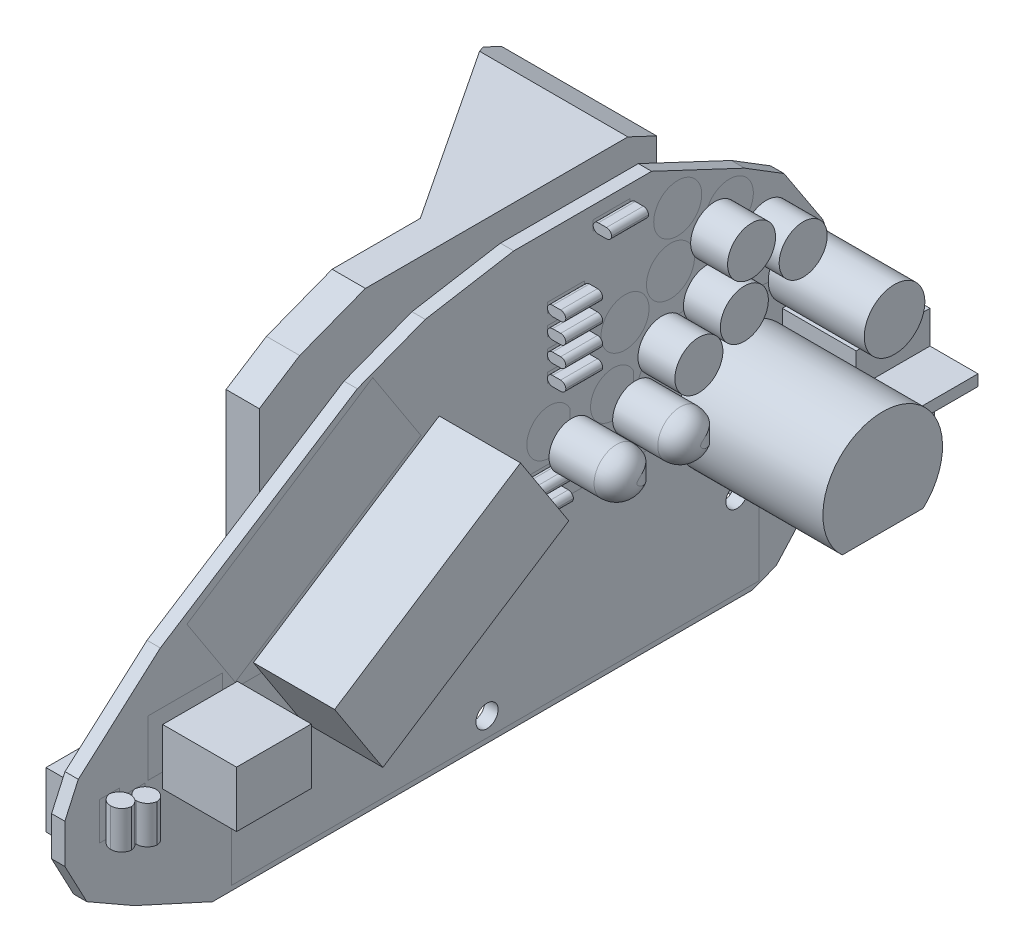
SolidWorks part; units mm, degrees
ref_plane "Alzado" through (0, 0, 0) normal (0, 0, 1) x (1, 0, 0)
ref_plane "Planta" through (0, 0, 0) normal (0, 1, 0) x (1, 0, 0)
ref_plane "Vista lateral" through (0, 0, 0) normal (1, 0, 0) x (0, 0, -1)
sketch "Croquis2" plane through (0, 0, 0) normal (1, 0, 0) x (0, 0, -1)
  line L0 (0.8299, 61.8219) -> (77.8633, 61.8219) construction
  line L1 (0, 0) -> (73, 0)
  line L2 (73, 0) -> (76.3008, 1.2365)
  line L3 (76.3008, 1.2365) -> (84.1489, 9.9615)
  line L4 (84.1489, 9.9615) -> (86.8383, 17.5094)
  line L5 (86.8383, 17.5094) -> (86.8383, 26.9193)
  line L6 (86.8383, 26.9193) -> (82.6155, 38.6955)
  line L7 (82.6155, 38.6955) -> (77.3688, 46.7034)
  line L9 (59.4482, 55.9264) -> (40.7811, 55.9264)
  line L10 (40.7811, 55.9264) -> (28.7946, 53.8855)
  line L11 (28.7946, 53.8855) -> (19.5987, 50.3479)
  line L12 (19.5987, 50.3479) -> (-7.0714, 33.2917)
  line L13 (-7.0714, 33.2917) -> (-18.1778, 23.4452)
  line L14 (-18.1778, 23.4452) -> (-19.9972, 19.4355)
  line L15 (-19.9972, 19.4355) -> (-19.9972, 14.1335)
  line L16 (-19.9972, 14.1335) -> (-17.0205, 8.5127)
  line L17 (-17.0205, 8.5127) -> (-10.6227, 4.8547)
  line L18 (-10.6227, 4.8547) -> (0, 0)
  line L19 (77.3688, 46.7034) -> (72.037, 49.9995)
  line L20 (72.037, 49.9995) -> (59.4482, 55.9264)
  dimension "D1" = 73
  dimension "D2" = 19.5987
  dimension "D3" = 28.7946
  dimension "D4" = 40.7811
  dimension "D5" = 59.4482
  dimension "D6" = 72.037
  dimension "D7" = 76.3008
  dimension "D8" = 77.3688
  dimension "D9" = 82.6155
  dimension "D10" = 84.1489
  dimension "D11" = 86.8383
  dimension "D12" = 7.0714
  dimension "D13" = 10.6227
  dimension "D14" = 17.0205
  dimension "D15" = 18.1778
  dimension "D16" = 19.9972
  dimension "D17" = 1.2365
  dimension "D18" = 4.8547
  dimension "D19" = 8.5127
  dimension "D20" = 9.9615
  dimension "D21" = 14.1335
  dimension "D22" = 17.5094
  dimension "D23" = 19.4355
  dimension "D24" = 23.4452
  dimension "D25" = 26.9193
  dimension "D26" = 33.2917
  dimension "D27" = 38.6955
  dimension "D28" = 46.7034
  dimension "D29" = 49.9995
  dimension "D30" = 50.3479
  dimension "D31" = 53.8855
  dimension "D32" = 55.9264
  dimension "D33" = 61.8219
sketch "Croquis4" plane through (0, 0, 0) normal (1, 0, 0) x (0, 0, -1)
  line L0 (-10.6227, 4.8547) -> (0, 0) construction
  line L1 (0, 0) -> (73, 0) construction
  line L2 (73, 0) -> (76.3008, 1.2365) construction
  line L3 (76.3008, 1.2365) -> (84.1489, 9.9615) construction
  line L4 (84.1489, 9.9615) -> (86.8383, 17.5094) construction
  line L5 (86.8383, 17.5094) -> (86.8383, 26.9193) construction
  line L6 (86.8383, 26.9193) -> (82.6155, 38.6955) construction
  line L7 (82.6155, 38.6955) -> (77.3688, 46.7034) construction
  line L8 (77.3688, 46.7034) -> (72.037, 49.9995) construction
  line L9 (72.037, 49.9995) -> (59.4482, 55.9264) construction
  line L10 (59.4482, 55.9264) -> (40.7811, 55.9264) construction
  line L11 (40.7811, 55.9264) -> (28.7946, 53.8855) construction
  line L12 (28.7946, 53.8855) -> (19.5987, 50.3479) construction
  line L13 (19.5987, 50.3479) -> (-7.0714, 33.2917) construction
  line L14 (-7.0714, 33.2917) -> (-18.1778, 23.4452) construction
  line L15 (-18.1778, 23.4452) -> (-19.9972, 19.4355) construction
  line L16 (-19.9972, 19.4355) -> (-19.9972, 14.1335) construction
  line L17 (-19.9972, 14.1335) -> (-17.0205, 8.5127) construction
  line L18 (-17.0205, 8.5127) -> (-10.6227, 4.8547) construction
  line L19 (-10.6227, 4.8547) -> (0, 0)
  line L20 (0, 0) -> (73, 0)
  line L21 (73, 0) -> (76.3008, 1.2365)
  line L22 (76.3008, 1.2365) -> (84.1489, 9.9615)
  line L23 (84.1489, 9.9615) -> (86.8383, 17.5094)
  line L24 (86.8383, 17.5094) -> (86.8383, 26.9193)
  line L25 (86.8383, 26.9193) -> (82.6155, 38.6955)
  line L26 (82.6155, 38.6955) -> (77.3688, 46.7034)
  line L27 (77.3688, 46.7034) -> (72.037, 49.9995)
  line L28 (72.037, 49.9995) -> (59.4482, 55.9264)
  line L29 (59.4482, 55.9264) -> (40.7811, 55.9264)
  line L30 (40.7811, 55.9264) -> (28.7946, 53.8855)
  line L31 (28.7946, 53.8855) -> (19.5987, 50.3479)
  line L32 (19.5987, 50.3479) -> (-7.0714, 33.2917)
  line L33 (-7.0714, 33.2917) -> (-18.1778, 23.4452)
  line L34 (-18.1778, 23.4452) -> (-19.9972, 19.4355)
  line L35 (-19.9972, 19.4355) -> (-19.9972, 14.1335)
  line L36 (-19.9972, 14.1335) -> (-17.0205, 8.5127)
  line L37 (-17.0205, 8.5127) -> (-10.6227, 4.8547)
extrude "Saliente-Extruir1" add sketch "Croquis4" along normal mid plane 1.8
sketch "Croquis5" plane through (0.9, 0, 0) normal (1, 0, 0) x (0, 0, -1)
  line L0 (-3.4698, 34.2759) -> (21.6903, 50.6151)
  line L1 (2.5913, 23.5294) -> (73.9913, 23.5294)
  line L2 (2.5913, 23.5294) -> (2.5913, 0.6294)
  line L3 (2.5913, 0.6294) -> (73.9913, 0.6294)
  line L4 (73.9913, 23.5294) -> (73.9913, 0.6294)
  line L5 (-8.7511, 26.1581) -> (1.3689, 26.1581)
  line L6 (-8.7511, 26.1581) -> (-8.7511, 18.5981)
  line L7 (-8.7511, 18.5981) -> (1.3689, 18.5981)
  line L8 (1.3689, 26.1581) -> (1.3689, 18.5981)
  line L9 (-15.2907, 19.6378) -> (-12.6307, 19.6378)
  line L10 (-15.2907, 19.6378) -> (-15.2907, 14.5278)
  line L11 (-15.2907, 14.5278) -> (-12.6307, 14.5278)
  line L12 (-12.6307, 19.6378) -> (-12.6307, 14.5278)
  line L13 (-11.8086, 18.4993) -> (-9.1486, 18.4993)
  line L14 (-11.8086, 18.4993) -> (-11.8086, 13.3893)
  line L15 (-11.8086, 13.3893) -> (-9.1486, 13.3893)
  line L16 (-9.1486, 18.4993) -> (-9.1486, 13.3893)
  line L17 (-3.4698, 34.2759) -> (3.0658, 24.2119)
  line L18 (21.6903, 50.6151) -> (28.226, 40.5511)
  line L19 (3.0658, 24.2119) -> (28.226, 40.5511)
  line L20 (0, 0) -> (73, 0) construction
  line L21 (75.6392, 27.0879) -> (85.7592, 27.0879)
  line L22 (75.6392, 27.0879) -> (75.6392, 19.5279)
  line L23 (75.6392, 19.5279) -> (85.7592, 19.5279)
  line L24 (85.7592, 27.0879) -> (85.7592, 19.5279)
  line L25 (74.1392, 28.0879) -> (84.1392, 28.0879)
  line L26 (74.1392, 28.0879) -> (74.1392, 34.0189)
  line L27 (74.1392, 34.0189) -> (84.1392, 34.0189)
  line L28 (84.1392, 28.0879) -> (84.1392, 34.0189)
  line L29 (48.3649, 30.915) -> (48.3649, 33.6844)
  line L30 (56.9859, 33.7818) -> (56.9859, 31.0124)
  line L32 (28.8788, 27.2935) -> (34.0788, 27.2935)
  line L33 (28.8788, 27.2935) -> (28.8788, 24.6435)
  line L34 (28.8788, 24.6435) -> (34.0788, 24.6435)
  line L35 (34.0788, 27.2935) -> (34.0788, 24.6435)
  line L36 (45.3296, 47.6238) -> (50.3296, 47.6238)
  line L37 (45.3296, 47.6238) -> (45.3296, 46.2938)
  line L38 (45.3296, 46.2938) -> (50.3296, 46.2938)
  line L39 (50.3296, 47.6238) -> (50.3296, 46.2938)
  line L40 (45.3296, 44.8838) -> (50.3296, 44.8838)
  line L41 (45.3296, 44.8838) -> (45.3296, 43.5538)
  line L42 (45.3296, 43.5538) -> (50.3296, 43.5538)
  line L43 (50.3296, 44.8838) -> (50.3296, 43.5538)
  line L44 (45.3296, 42.1438) -> (50.3296, 42.1438)
  line L45 (45.3296, 42.1438) -> (45.3296, 40.8138)
  line L46 (45.3296, 40.8138) -> (50.3296, 40.8138)
  line L47 (50.3296, 42.1438) -> (50.3296, 40.8138)
  line L48 (45.3296, 39.4038) -> (50.3296, 39.4038)
  line L49 (45.3296, 39.4038) -> (45.3296, 38.0738)
  line L50 (45.3296, 38.0738) -> (50.3296, 38.0738)
  line L51 (50.3296, 39.4038) -> (50.3296, 38.0738)
  line L52 (41.3607, 28.5694) -> (46.3607, 28.5694)
  line L53 (41.3607, 28.5694) -> (41.3607, 27.2394)
  line L54 (41.3607, 27.2394) -> (46.3607, 27.2394)
  line L55 (46.3607, 28.5694) -> (46.3607, 27.2394)
  line L56 (41.3607, 26.0194) -> (46.3607, 26.0194)
  line L57 (41.3607, 26.0194) -> (41.3607, 24.6894)
  line L58 (41.3607, 24.6894) -> (46.3607, 24.6894)
  line L59 (46.3607, 26.0194) -> (46.3607, 24.6894)
  line L60 (51.5296, 54.1938) -> (56.5296, 54.1938)
  line L61 (51.5296, 54.1938) -> (51.5296, 52.8638)
  line L62 (51.5296, 52.8638) -> (56.5296, 52.8638)
  line L63 (56.5296, 54.1938) -> (56.5296, 52.8638)
  circle A0 centre (65.2392, 29.5) radius 8.1
  circle A1 centre (75.3392, 39.1189) radius 4.1
  arc A2 (48.3649, 33.6844) -> (48.3649, 30.915) centre (45.6249, 32.2997) ccw
  arc A3 (56.9859, 33.7818) -> (56.9859, 31.0124) centre (54.2459, 32.3971) ccw
  circle A4 centre (69.9704, 46.5024) radius 3.25
  circle A5 centre (62.9828, 49.8363) radius 3.25
  circle A6 centre (62.0052, 42.9497) radius 3.25
  circle A7 centre (55.8488, 40.0099) radius 3.25
  point P37 (73.3392, 29.5)
  point P39 (75.3392, 35.0189)
  dimension "D25" = 16.2
  dimension "D28" = 8.2
  dimension "D31" = 6.14
  dimension "D53" = 6.5
  dimension "D1" = 71.4
  dimension "D2" = 22.9
  dimension "D3" = 2.5913
  dimension "D4" = 0.6294
  dimension "D5" = 10.12
  dimension "D6" = 7.56
  dimension "D7" = 18.5981
  dimension "D8" = 1.3689
  dimension "D9" = 2.66
  dimension "D10" = 5.11
  dimension "D11" = 14.5278
  dimension "D12" = 12.6307
  dimension "D13" = 13.3893
  dimension "D14" = 9.1486
  dimension "D15" = 12
  dimension "D16" = 30
  dimension "D17" = 33
  dimension "D18" = 24.2119
  dimension "D19" = 3.0658
  dimension "D20" = 19.5279
  dimension "D21" = 75.6392
  dimension "D22" = 1
  dimension "D23" = 5.931
  dimension "20" = 10
  dimension "D24" = 1.5
  dimension "D26" = 29.5
  dimension "D27" = 0.8
  dimension "D29" = 1
  dimension "D30" = 1.2
  dimension "D32" = 32.2997
  dimension "D33" = 44.256
  dimension "D34" = 8.621
  dimension "D35" = 0.0974
  dimension "D36" = 2.74
  dimension "D37" = 2.65
  dimension "D38" = 5.2
  dimension "D39" = 24.6435
  dimension "D40" = 28.8788
  dimension "D41" = 1.33
  dimension "D42" = 5
  dimension "D43" = 1.41
  dimension "D44" = 1.41
  dimension "D45" = 1.41
  dimension "D46" = 38.0738
  dimension "D47" = 25.3096
  dimension "D48" = 1.16
  dimension "D49" = 1.22
  dimension "D50" = 27.6307
  dimension "D51" = 1.2
  dimension "D52" = 5.24
  dimension "D54" = 55.8488
  dimension "D55" = 40.0099
  dimension "D56" = 6.1565
  dimension "D57" = 2.9399
  dimension "D58" = 6.8866
  dimension "D59" = 0.9775
  dimension "D60" = 6.9876
  dimension "D61" = 3.3339
split line "Línea de partición1"
sketch "Croquis6" plane through (-0.9, 0, 0) normal (-1, 0, 0) x (0, 0, 1)
  line L0 (-2.5913, 23.5294) -> (-2.5913, 0.6294) construction
  line L1 (-2.5913, 0.6294) -> (-73.9913, 0.6294) construction
  line L2 (-73.9913, 0.6294) -> (-73.9913, 23.5294) construction
  line L4 (-2.5913, 23.5294) -> (-2.5913, 0.6294)
  line L5 (-2.5913, 0.6294) -> (-73.9913, 0.6294)
  line L6 (-73.9913, 0.6294) -> (-73.9913, 23.5294)
  line L7 (-73.9913, 23.5294) -> (-2.5913, 23.5294)
  line L8 (8.7511, 18.5981) -> (-1.3689, 18.5981) construction
  line L9 (-81.9748, 18.5065) -> (-74.4148, 18.5065)
  line L10 (-81.9748, 18.5065) -> (-81.9748, 8.3865)
  line L11 (-81.9748, 8.3865) -> (-74.4148, 8.3865)
  line L12 (-74.4148, 18.5065) -> (-74.4148, 8.3865)
  line L13 (8.7511, 26.1581) -> (8.7511, 18.5981) construction
  line L14 (-85.7592, 27.0879) -> (-75.6392, 27.0879) construction
  line L15 (-75.6392, 27.0879) -> (-75.6392, 19.5279) construction
  line L17 (-1.3689, 13.2116) -> (8.7511, 13.2116)
  line L18 (-1.3689, 13.2116) -> (-1.3689, 5.6516)
  line L19 (-1.3689, 5.6516) -> (8.7511, 5.6516)
  line L20 (8.7511, 13.2116) -> (8.7511, 5.6516)
  line L21 (-67.93, 23.8894) -> (-14.13, 23.8894)
  line L22 (-67.93, 23.8894) -> (-67.93, 53.7694)
  line L23 (-67.93, 53.7694) -> (-14.13, 53.7694)
  line L24 (-14.13, 23.8894) -> (-14.13, 53.7694)
  dimension "D1" = 0.4234
  dimension "D2" = 5.0229
  dimension "D3" = 5.6516
  dimension "D4" = 29.88
  dimension "D5" = 53.8
  dimension "D6" = 0.36
  dimension "D7" = 14.13
split line "Línea de partición2"
sketch "Croquis7" plane through (0.9, 0, 0) normal (1, 0, 0) x (0, 0, -1)
  line L4 (1.3689, 26.1581) -> (-8.7511, 26.1581)
  line L5 (-8.7511, 26.1581) -> (-8.7511, 18.5981)
  line L6 (-8.7511, 18.5981) -> (1.3689, 18.5981)
  line L7 (1.3689, 18.5981) -> (1.3689, 26.1581)
  line L8 (1.3689, 26.1581) -> (-8.7511, 26.1581)
  line L9 (-8.7511, 26.1581) -> (-8.7511, 18.5981)
  line L10 (-8.7511, 18.5981) -> (1.3689, 18.5981)
  line L11 (1.3689, 18.5981) -> (1.3689, 26.1581)
  line L12 (85.7592, 27.0879) -> (75.6392, 27.0879)
  line L13 (75.6392, 27.0879) -> (75.6392, 19.5279)
  line L14 (75.6392, 19.5279) -> (85.7592, 19.5279)
  line L15 (85.7592, 19.5279) -> (85.7592, 27.0879)
  line L16 (85.7592, 27.0879) -> (75.6392, 27.0879)
  line L17 (75.6392, 27.0879) -> (75.6392, 19.5279)
  line L18 (75.6392, 19.5279) -> (85.7592, 19.5279)
  line L19 (85.7592, 19.5279) -> (85.7592, 27.0879)
  dimension "D1" = 0
  dimension "D2" = 0
extrude "Saliente-Extruir2" add sketch "Croquis7" along normal blind 10 from offset 2 separate body
sketch "Croquis8" plane through (0.9, 0, 0) normal (1, 0, 0) x (0, 0, -1)
  line L4 (21.6903, 50.6151) -> (-3.4698, 34.2759)
  line L5 (-3.4698, 34.2759) -> (3.0658, 24.2119)
  line L6 (3.0658, 24.2119) -> (28.226, 40.5511)
  line L7 (28.226, 40.5511) -> (21.6903, 50.6151)
  line L8 (21.6903, 50.6151) -> (-3.4698, 34.2759)
  line L9 (-3.4698, 34.2759) -> (3.0658, 24.2119)
  line L10 (3.0658, 24.2119) -> (28.226, 40.5511)
  line L11 (28.226, 40.5511) -> (21.6903, 50.6151)
  dimension "D1" = 0
extrude "Saliente-Extruir3" add sketch "Croquis8" along normal blind 11 from offset 9 separate body
sketch "Croquis9" plane through (0.9, 0, 0) normal (1, 0, 0) x (0, 0, -1)
  line L1 (59.7654, 23.5294) -> (70.7129, 23.5294)
  line L2 (59.7654, 23.5294) -> (70.7129, 23.5294)
  arc A1 (70.7129, 23.5294) -> (59.7654, 23.5294) centre (65.2392, 29.5) ccw
  arc A3 (70.7129, 23.5294) -> (59.7654, 23.5294) centre (65.2392, 29.5) ccw
  dimension "D1" = 0
extrude "Saliente-Extruir4" add sketch "Croquis9" along normal blind 20 from offset 5.5 separate body
sketch "Croquis10" plane through (0.9, 0, 0) normal (1, 0, 0) x (0, 0, -1)
  circle A0 centre (69.9704, 46.5024) radius 3.25 construction
  circle A1 centre (55.8488, 40.0099) radius 3.25
  circle A2 centre (55.8488, 40.0099) radius 3.25
  circle A3 centre (62.0052, 42.9497) radius 3.25
  circle A4 centre (62.0052, 42.9497) radius 3.25
  circle A5 centre (62.9828, 49.8363) radius 3.25 construction
  circle A6 centre (69.9704, 46.5024) radius 3.25
  circle A7 centre (62.9828, 49.8363) radius 3.25
  dimension "D1" = 0
  dimension "D2" = 0
extrude "Saliente-Extruir5" add sketch "Croquis10" along normal blind 5 from offset 5 separate body
sketch "Croquis11" plane through (0.9, 0, 0) normal (1, 0, 0) x (0, 0, -1)
  line L0 (34.0788, 27.2935) -> (28.8788, 27.2935) construction
  line L1 (28.8788, 27.2935) -> (28.8788, 24.6435) construction
  line L2 (28.8788, 24.6435) -> (34.0788, 24.6435) construction
  line L3 (34.0788, 24.6435) -> (34.0788, 27.2935) construction
  line L4 (-9.1486, 18.4993) -> (-11.8086, 18.4993) construction
  line L5 (-11.8086, 18.4993) -> (-11.8086, 13.3893) construction
  line L6 (-11.8086, 13.3893) -> (-9.1486, 13.3893) construction
  line L7 (-9.1486, 13.3893) -> (-9.1486, 18.4993) construction
  line L8 (-12.6307, 19.6378) -> (-15.2907, 19.6378) construction
  line L9 (-15.2907, 19.6378) -> (-15.2907, 14.5278) construction
  line L10 (-15.2907, 14.5278) -> (-12.6307, 14.5278) construction
  line L11 (-12.6307, 14.5278) -> (-12.6307, 19.6378) construction
  line L12 (34.0788, 27.2935) -> (28.8788, 27.2935)
  line L13 (28.8788, 27.2935) -> (28.8788, 24.6435)
  line L14 (28.8788, 24.6435) -> (34.0788, 24.6435)
  line L15 (34.0788, 24.6435) -> (34.0788, 27.2935)
  line L16 (-9.1486, 18.4993) -> (-11.8086, 18.4993)
  line L17 (-11.8086, 18.4993) -> (-11.8086, 13.3893)
  line L18 (-11.8086, 13.3893) -> (-9.1486, 13.3893)
  line L19 (-9.1486, 13.3893) -> (-9.1486, 18.4993)
  line L20 (-12.6307, 19.6378) -> (-15.2907, 19.6378)
  line L21 (-15.2907, 19.6378) -> (-15.2907, 14.5278)
  line L22 (-15.2907, 14.5278) -> (-12.6307, 14.5278)
  line L23 (-12.6307, 14.5278) -> (-12.6307, 19.6378)
extrude "Saliente-Extruir6" add sketch "Croquis11" along normal blind 3 separate body
fillet "Redondeo1" radius 1.5 4 edges at (3.9, 17.0828, 12.6307) (3.9, 17.0828, 15.2907) (0.9, 17.0828, 12.6307) (0.9, 17.0828, 15.2907)
fillet "Redondeo2" radius 1.5 4 edges at (0.9, 15.9443, 11.8086) (0.9, 15.9443, 9.1486) (3.9, 15.9443, 9.1486) (3.9, 15.9443, 11.8086)
fillet "Redondeo3" radius 1.5 4 edges at (0.9, 27.2935, -31.4788) (0.9, 24.6435, -31.4788) (3.9, 24.6435, -31.4788) (3.9, 27.2935, -31.4788)
sketch "Croquis12" plane through (0.9, 0, 0) normal (1, 0, 0) x (0, 0, -1)
  line L0 (46.3607, 26.0194) -> (41.3607, 26.0194) construction
  line L1 (41.3607, 26.0194) -> (41.3607, 24.6894) construction
  line L2 (41.3607, 24.6894) -> (46.3607, 24.6894) construction
  line L3 (46.3607, 24.6894) -> (46.3607, 26.0194) construction
  line L4 (46.3607, 28.5694) -> (41.3607, 28.5694) construction
  line L5 (41.3607, 28.5694) -> (41.3607, 27.2394) construction
  line L6 (41.3607, 27.2394) -> (46.3607, 27.2394) construction
  line L7 (46.3607, 27.2394) -> (46.3607, 28.5694) construction
  line L8 (50.3296, 39.4038) -> (45.3296, 39.4038) construction
  line L9 (45.3296, 39.4038) -> (45.3296, 38.0738) construction
  line L10 (45.3296, 38.0738) -> (50.3296, 38.0738) construction
  line L11 (50.3296, 38.0738) -> (50.3296, 39.4038) construction
  line L12 (50.3296, 42.1438) -> (45.3296, 42.1438) construction
  line L13 (45.3296, 42.1438) -> (45.3296, 40.8138) construction
  line L14 (45.3296, 40.8138) -> (50.3296, 40.8138) construction
  line L15 (50.3296, 40.8138) -> (50.3296, 42.1438) construction
  line L16 (50.3296, 44.8838) -> (45.3296, 44.8838) construction
  line L17 (45.3296, 44.8838) -> (45.3296, 43.5538) construction
  line L18 (45.3296, 43.5538) -> (50.3296, 43.5538) construction
  line L19 (50.3296, 43.5538) -> (50.3296, 44.8838) construction
  line L20 (50.3296, 47.6238) -> (45.3296, 47.6238) construction
  line L21 (45.3296, 47.6238) -> (45.3296, 46.2938) construction
  line L22 (45.3296, 46.2938) -> (50.3296, 46.2938) construction
  line L23 (50.3296, 46.2938) -> (50.3296, 47.6238) construction
  line L24 (56.5296, 54.1938) -> (51.5296, 54.1938) construction
  line L25 (51.5296, 54.1938) -> (51.5296, 52.8638) construction
  line L26 (51.5296, 52.8638) -> (56.5296, 52.8638) construction
  line L27 (56.5296, 52.8638) -> (56.5296, 54.1938) construction
  line L28 (46.3607, 26.0194) -> (41.3607, 26.0194)
  line L29 (41.3607, 26.0194) -> (41.3607, 24.6894)
  line L30 (41.3607, 24.6894) -> (46.3607, 24.6894)
  line L31 (46.3607, 24.6894) -> (46.3607, 26.0194)
  line L32 (46.3607, 28.5694) -> (41.3607, 28.5694)
  line L33 (41.3607, 28.5694) -> (41.3607, 27.2394)
  line L34 (41.3607, 27.2394) -> (46.3607, 27.2394)
  line L35 (46.3607, 27.2394) -> (46.3607, 28.5694)
  line L36 (50.3296, 39.4038) -> (45.3296, 39.4038)
  line L37 (45.3296, 39.4038) -> (45.3296, 38.0738)
  line L38 (45.3296, 38.0738) -> (50.3296, 38.0738)
  line L39 (50.3296, 38.0738) -> (50.3296, 39.4038)
  line L40 (50.3296, 42.1438) -> (45.3296, 42.1438)
  line L41 (45.3296, 42.1438) -> (45.3296, 40.8138)
  line L42 (45.3296, 40.8138) -> (50.3296, 40.8138)
  line L43 (50.3296, 40.8138) -> (50.3296, 42.1438)
  line L44 (50.3296, 44.8838) -> (45.3296, 44.8838)
  line L45 (45.3296, 44.8838) -> (45.3296, 43.5538)
  line L46 (45.3296, 43.5538) -> (50.3296, 43.5538)
  line L47 (50.3296, 43.5538) -> (50.3296, 44.8838)
  line L48 (50.3296, 47.6238) -> (45.3296, 47.6238)
  line L49 (45.3296, 47.6238) -> (45.3296, 46.2938)
  line L50 (45.3296, 46.2938) -> (50.3296, 46.2938)
  line L51 (50.3296, 46.2938) -> (50.3296, 47.6238)
  line L52 (56.5296, 54.1938) -> (51.5296, 54.1938)
  line L53 (51.5296, 54.1938) -> (51.5296, 52.8638)
  line L54 (51.5296, 52.8638) -> (56.5296, 52.8638)
  line L55 (56.5296, 52.8638) -> (56.5296, 54.1938)
extrude "Saliente-Extruir7" add sketch "Croquis12" along normal blind 2.5 separate body
fillet "Redondeo4" radius 0.7 4 edges at (0.9, 28.5694, -43.8607) (0.9, 27.2394, -43.8607) (3.4, 28.5694, -43.8607) (3.4, 27.2394, -43.8607)
fillet "Redondeo5" radius 0.7 4 edges at (0.9, 24.6894, -43.8607) (3.4, 24.6894, -43.8607) (0.9, 26.0194, -43.8607) (3.4, 26.0194, -43.8607)
fillet "Redondeo6" radius 0.7 4 edges at (0.9, 39.4038, -47.8296) (3.4, 39.4038, -47.8296) (3.4, 38.0738, -47.8296) (0.9, 38.0738, -47.8296)
fillet "Redondeo7" radius 0.7 4 edges at (0.9, 40.8138, -47.8296) (0.9, 42.1438, -47.8296) (3.4, 42.1438, -47.8296) (3.4, 40.8138, -47.8296)
fillet "Redondeo8" radius 0.7 4 edges at (0.9, 44.8838, -47.8296) (3.4, 44.8838, -47.8296) (0.9, 43.5538, -47.8296) (3.4, 43.5538, -47.8296)
fillet "Redondeo9" radius 0.7 4 edges at (0.9, 46.2938, -47.8296) (0.9, 47.6238, -47.8296) (3.4, 47.6238, -47.8296) (3.4, 46.2938, -47.8296)
fillet "Redondeo10" radius 0.7 4 edges at (0.9, 54.1938, -54.0296) (0.9, 52.8638, -54.0296) (3.4, 52.8638, -54.0296) (3.4, 54.1938, -54.0296)
sketch "Croquis13" plane through (0.9, 0, 0) normal (1, 0, 0) x (0, 0, -1)
  circle A1 centre (75.3392, 39.1189) radius 4.1
  circle A2 centre (75.3392, 39.1189) radius 4.1
  dimension "D1" = 0
extrude "Saliente-Extruir8" add sketch "Croquis13" along normal blind 13 from offset 4 separate body
sketch "Croquis14" plane through (0.9, 0, 0) normal (1, 0, 0) x (0, 0, -1)
  line L0 (56.9859, 31.0124) -> (56.9859, 33.7818) construction
  line L1 (48.3649, 30.915) -> (48.3649, 33.6844) construction
  line L2 (56.9859, 31.0124) -> (56.9859, 33.7818)
  line L3 (48.3649, 30.915) -> (48.3649, 33.6844)
  arc A0 (56.9859, 33.7818) -> (56.9859, 31.0124) centre (54.2459, 32.3971) ccw construction
  arc A1 (48.3649, 33.6844) -> (48.3649, 30.915) centre (45.6249, 32.2997) ccw construction
  arc A2 (56.9859, 33.7818) -> (56.9859, 31.0124) centre (54.2459, 32.3971) ccw
  arc A3 (48.3649, 33.6844) -> (48.3649, 30.915) centre (45.6249, 32.2997) ccw
extrude "Saliente-Extruir9" add sketch "Croquis14" along normal blind 9 from offset 3 separate body
fillet "Redondeo11" radius 2.9 2 edges at (12.9, 32.2997, -48.3649) (12.9, 32.2997, -42.5549)
fillet "Redondeo12" radius 2.9 2 edges at (12.9, 32.3971, -56.9859) (12.9, 32.3971, -51.1759)
sketch "Croquis15" plane through (0.9, 0, 0) normal (1, 0, 0) x (0, 0, -1)
  line L4 (84.1392, 34.0189) -> (74.1392, 34.0189)
  line L5 (74.1392, 34.0189) -> (74.1392, 28.0879)
  line L6 (74.1392, 28.0879) -> (84.1392, 28.0879)
  line L7 (84.1392, 28.0879) -> (84.1392, 34.0189)
  line L8 (84.1392, 34.0189) -> (74.1392, 34.0189)
  line L9 (74.1392, 34.0189) -> (74.1392, 28.0879)
  line L10 (74.1392, 28.0879) -> (84.1392, 28.0879)
  line L11 (84.1392, 28.0879) -> (84.1392, 34.0189)
  dimension "D1" = 0
extrude "Saliente-Extruir10" add sketch "Croquis15" along normal blind 10 from offset 3 separate body
sketch "Croquis16" plane through (13.9, 0, 0) normal (1, 0, 0) x (0, 0, -1)
  line L0 (84.1392, 28.0879) -> (84.1392, 34.0189) construction
  line L1 (74.1392, 28.0879) -> (84.1392, 28.0879)
  line L2 (74.1392, 28.0879) -> (74.1392, 29.5879)
  line L3 (74.1392, 29.5879) -> (84.1392, 29.5879)
  line L4 (84.1392, 28.0879) -> (84.1392, 29.5879)
  dimension "D1" = 1.5
extrude "Saliente-Extruir11" add sketch "Croquis16" along normal blind 6.5 separate body
sketch "Croquis17" plane through (-0.9, 0, 0) normal (-1, 0, 0) x (0, 0, 1)
  line L0 (-1.3689, 13.2116) -> (-1.3689, 5.6516) construction
  line L1 (-1.3689, 5.6516) -> (8.7511, 5.6516) construction
  line L2 (8.7511, 5.6516) -> (8.7511, 13.2116) construction
  line L3 (8.7511, 13.2116) -> (-1.3689, 13.2116) construction
  line L4 (-81.9748, 18.5065) -> (-81.9748, 8.3865) construction
  line L5 (-81.9748, 8.3865) -> (-74.4148, 8.3865) construction
  line L6 (-74.4148, 8.3865) -> (-74.4148, 18.5065) construction
  line L7 (-74.4148, 18.5065) -> (-81.9748, 18.5065) construction
  line L8 (-1.3689, 13.2116) -> (-1.3689, 5.6516)
  line L9 (-1.3689, 5.6516) -> (8.7511, 5.6516)
  line L10 (8.7511, 5.6516) -> (8.7511, 13.2116)
  line L11 (8.7511, 13.2116) -> (-1.3689, 13.2116)
  line L12 (-81.9748, 18.5065) -> (-81.9748, 8.3865)
  line L13 (-81.9748, 8.3865) -> (-74.4148, 8.3865)
  line L14 (-74.4148, 8.3865) -> (-74.4148, 18.5065)
  line L15 (-74.4148, 18.5065) -> (-81.9748, 18.5065)
extrude "Saliente-Extruir12" add sketch "Croquis17" along normal blind 10 from offset 2 separate body
sketch "Croquis18" plane through (-0.9, 0, 0) normal (-1, 0, 0) x (0, 0, 1)
  line L7 (-67.93, 51.9331) -> (-67.93, 23.8894)
  line L8 (-67.93, 23.8894) -> (-14.13, 23.8894)
  line L9 (-14.13, 23.8894) -> (-14.13, 46.8505)
  line L10 (-14.13, 46.8505) -> (-19.5987, 50.3479)
  line L11 (-19.5987, 50.3479) -> (-28.4928, 53.7694)
  line L12 (-28.4928, 53.7694) -> (-64.0297, 53.7694)
  line L13 (-64.0297, 53.7694) -> (-67.93, 51.9331)
  line L14 (-67.93, 51.9331) -> (-67.93, 23.8894)
  line L15 (-67.93, 23.8894) -> (-14.13, 23.8894)
  line L16 (-14.13, 23.8894) -> (-14.13, 46.8505)
  line L17 (-14.13, 46.8505) -> (-19.5987, 50.3479)
  line L18 (-19.5987, 50.3479) -> (-28.4928, 53.7694)
  line L19 (-28.4928, 53.7694) -> (-64.0297, 53.7694)
  line L20 (-64.0297, 53.7694) -> (-67.93, 51.9331)
  dimension "D1" = 0
extrude "Saliente-Extruir13" add sketch "Croquis18" along normal blind 21 from offset 6 separate body
sketch "Croquis19" plane through (-27.9, 0, 0) normal (-1, 0, 0) x (0, 0, 1)
  line L7 (-65.43, 25.3894) -> (-65.43, 52.2694)
  line L8 (-67.93, 23.8894) -> (-67.93, 51.9331) construction
  line L9 (-65.43, 25.3894) -> (-14.13, 25.3894)
  line L10 (-14.13, 46.8505) -> (-14.13, 23.8894) construction
  line L11 (-14.13, 25.3894) -> (-14.13, 52.2694)
  line L12 (-14.13, 52.2694) -> (-65.43, 52.2694)
  line L14 (-63.6943, 52.2694) -> (-66.43, 50.9814)
  line L15 (-66.43, 50.9814) -> (-66.43, 25.3894)
  line L16 (-66.43, 25.3894) -> (-15.63, 25.3894)
  line L17 (-15.63, 25.3894) -> (-15.63, 46.0293)
  line L18 (-15.63, 46.0293) -> (-20.279, 49.0024)
  line L19 (-20.279, 49.0024) -> (-28.7714, 52.2694)
  line L20 (-28.7714, 52.2694) -> (-63.6943, 52.2694)
  line L21 (-63.6943, 52.2694) -> (-66.43, 50.9814) construction
  line L22 (-66.43, 50.9814) -> (-66.43, 25.3894) construction
  line L23 (-66.43, 25.3894) -> (-15.63, 25.3894) construction
  line L24 (-15.63, 25.3894) -> (-15.63, 46.0293) construction
  line L25 (-15.63, 46.0293) -> (-20.279, 49.0024) construction
  line L26 (-20.279, 49.0024) -> (-28.7714, 52.2694) construction
  line L27 (-28.7714, 52.2694) -> (-63.6943, 52.2694) construction
  dimension "D2" = 2.5
  dimension "D1" = 1.5
extrude "Cortar-Extruir1" cut sketch "Croquis19" against normal blind 16.5
sketch "Croquis20" plane through (0, 23.8894, 0) normal (0, -1, 0) x (1, 0, 0)
  line L0 (-11.4, -65.43) -> (-27.9, -65.43) construction
  line L1 (-27.9, -65.43) -> (-11.4, -40.43) construction
  line L2 (-11.4, -65.43) -> (-11.4, -14.13) construction
  line L3 (-11.4, -40.43) -> (-11.4, -65.43) construction
  line L4 (-27.9, -65.43) -> (-30.3955, -65.43)
  line L5 (-30.3955, -65.43) -> (-30.3955, -11.992)
  line L6 (-30.3955, -11.992) -> (-11.4, -11.992)
  line L7 (-11.4, -11.992) -> (-11.4, -40.43)
  line L8 (-11.4, -40.43) -> (-27.9, -65.43)
  dimension "D1" = 25
extrude "Cortar-Extruir2" cut sketch "Croquis20" against normal up to surface (29.88 mm away) up to face at (-17.4, 53.7694, -46.2613)
sketch "Croquis21" plane through (0.9, 0, 0) normal (1, 0, 0) x (0, 0, -1)
  line L0 (73.9913, 23.5294) -> (70.7129, 23.5294) construction
  circle A0 centre (71.0022, 12.1131) radius 1.5
  circle A1 centre (37.1563, 20.6265) radius 1.5
  circle A2 centre (37.1563, 3.2108) radius 1.5
  dimension "D1" = 3
  dimension "D2" = 34.565
  dimension "D3" = 68.4108
  dimension "D4" = 2.9029
  dimension "D5" = 11.4163
  dimension "D6" = 20.3185
extrude "Cortar-Extruir3" cut sketch "Croquis21" against normal up to next (1.8 mm away)
